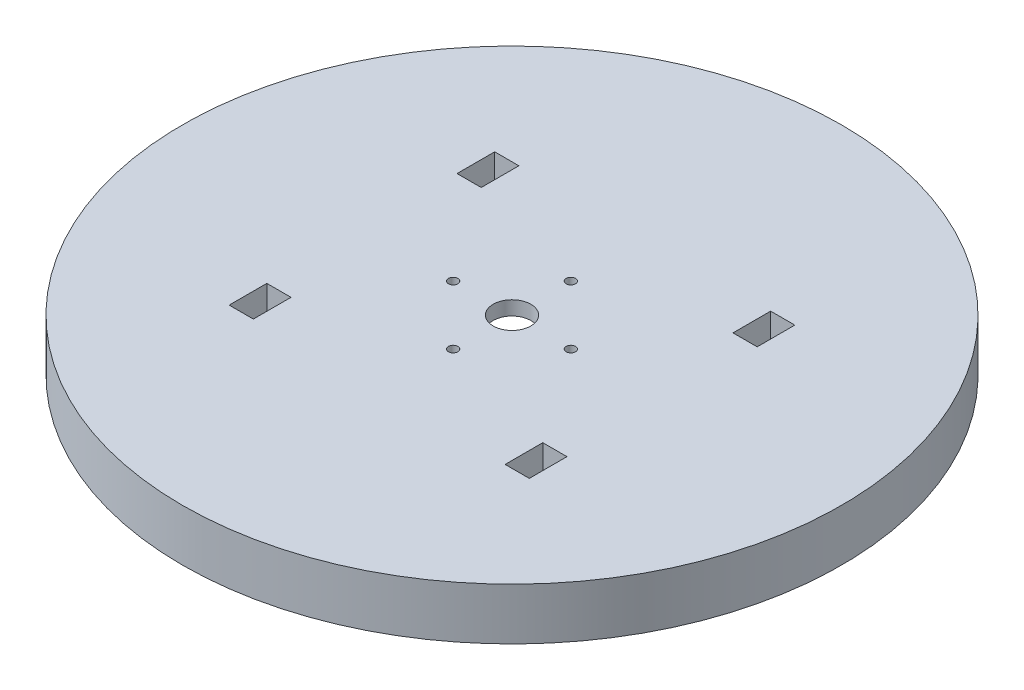
SolidWorks part; units mm, degrees
material "ABS"
ref_plane "Front Plane" through (0, 0, 0) normal (0, 0, 1) x (1, 0, 0)
ref_plane "Top Plane" through (0, 0, 0) normal (0, 1, 0) x (1, 0, 0)
ref_plane "Right Plane" through (0, 0, 0) normal (1, 0, 0) x (0, 0, -1)
sketch "Sketch1" plane through (0, 0, 0) normal (0, 1, 0) x (1, 0, 0)
  line L0 (-22.5, 0) -> (-67.5, 0) construction
  line L1 (-26.7381, -20.2) -> (-26.7381, 20.2) construction
  line L2 (-26.7381, -28.2) -> (-31.8764, -28.2)
  line L3 (-26.7381, 20.2) -> (-31.8764, 20.2)
  line L4 (-26.7381, 20.2) -> (-26.7381, 28.2)
  line L5 (-26.7381, 28.2) -> (-31.8764, 28.2)
  line L6 (-31.8764, 20.2) -> (-31.8764, 28.2)
  line L7 (-31.8764, -20.2) -> (-31.8764, -28.2)
  line L8 (-26.7381, -20.2) -> (-31.8764, -20.2)
  line L9 (-26.7381, -20.2) -> (-26.7381, -28.2)
  line L11 (26.7381, -20.2) -> (26.7381, 20.2) construction
  line L12 (26.7381, -20.2) -> (26.7381, -28.2)
  line L13 (26.7381, -20.2) -> (31.8764, -20.2)
  line L14 (31.8764, -20.2) -> (31.8764, -28.2)
  line L15 (26.7381, -28.2) -> (31.8764, -28.2)
  line L16 (26.7381, 28.2) -> (31.8764, 28.2)
  line L17 (31.8764, 20.2) -> (31.8764, 28.2)
  line L18 (26.7381, 20.2) -> (31.8764, 20.2)
  line L19 (26.7381, 20.2) -> (26.7381, 28.2)
  circle A0 centre (0, 0) radius 67.5
  circle A1 centre (0, 0) radius 70
  circle A2 centre (0, 0) radius 22.5
  circle A3 centre (0, 12.5) radius 1
  circle A4 centre (0, -12.5) radius 1
  circle A5 centre (12.5, 0) radius 1
  circle A6 centre (-12.5, 0) radius 1
  circle A7 centre (0, 0) radius 4
  circle A8 centre (0, 0) radius 77.5385
  point P10 (-26.7381, 0)
  dimension "D1" = 135
  dimension "D2" = 140
  dimension "D3" = 12.5
  dimension "D7" = 2
  dimension "D8" = 2
  dimension "D9" = 8
  dimension "D10" = 45
  dimension "D4" = 20.2
  dimension "D5" = 8
  dimension "D6" = 12.5
  dimension "D11" = 5.1383
extrude "Boss-Extrude7" add sketch "Sketch1" against normal blind 3 contours A2 A7 A4 A3 A5 A6 region at (-21.8636, 0, 0)
extrude "Boss-Extrude8" add sketch "Sketch1<15>" against normal blind 8 contours A0 A2 L18 L19 L16 L17 L8 L9 L2 L7 L3 L6 L5 L4 L15 L12 L13 L14 region at (-65.5908, 0, 0)
sketch "Sketch1<15>" plane through (0, 0, 0) normal (0, 1, 0) x (1, 0, 0) same geometry as "Sketch1"
extrude "Boss-Extrude10" add sketch "Sketch1<20>" against normal blind 11 contours A1 A0 region at (-68.0201, 0, 0)
sketch "Sketch1<20>" plane through (0, 0, 0) normal (0, 1, 0) x (1, 0, 0) same geometry as "Sketch1"
